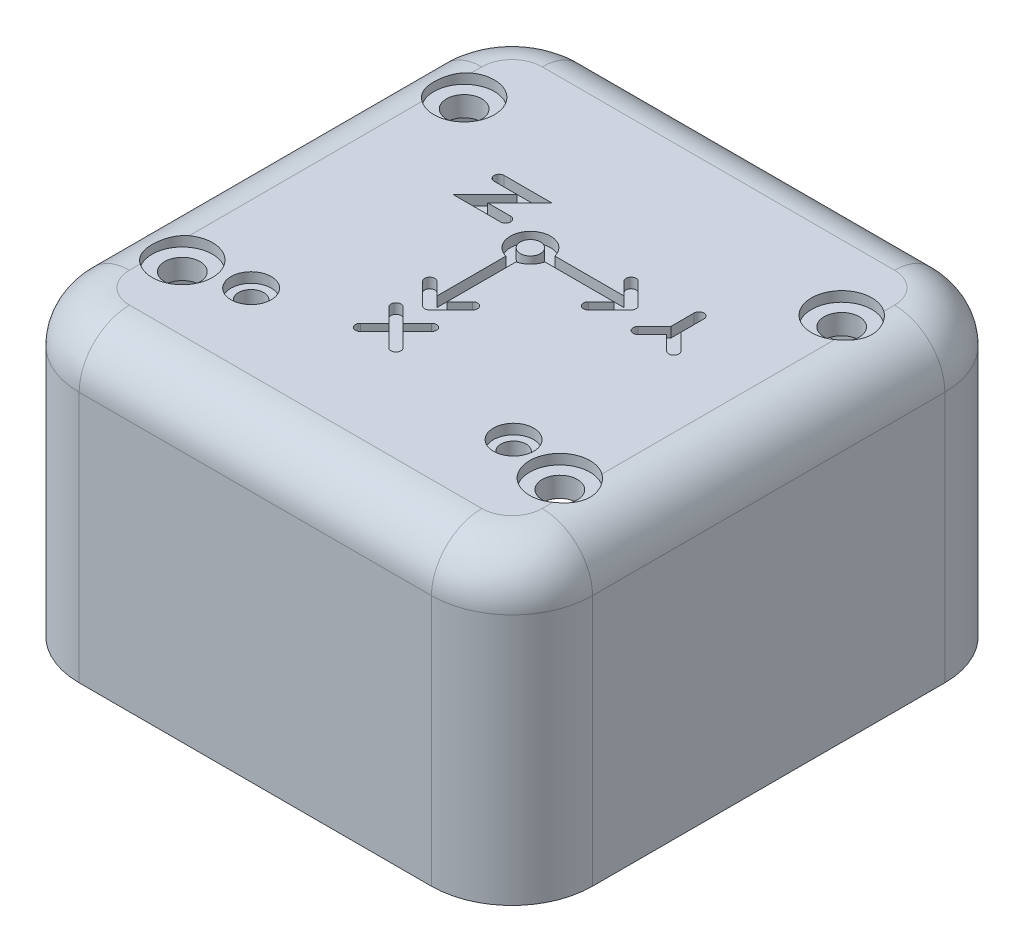
SolidWorks part; units mm, degrees
ref_plane "Front Plane" through (0, 0, 0) normal (0, 0, 1) x (1, 0, 0)
ref_plane "Top Plane" through (0, 0, 0) normal (0, 1, 0) x (1, 0, 0)
ref_plane "Right Plane" through (0, 0, 0) normal (1, 0, 0) x (0, 0, -1)
sketch "Sketch1" plane through (0, 0, 0) normal (0, 1, 0) x (1, 0, 0)
  line L1 (8, 0) -> (43, 0)
  line L2 (0, 8) -> (0, 43)
  line L3 (8, 51) -> (43, 51)
  line L4 (51, 8) -> (51, 43)
  arc A0 (43, 51) -> (51, 43) centre (43, 43) cw
  arc A1 (43, 0) -> (51, 8) centre (43, 8) ccw
  arc A2 (8, 0) -> (0, 8) centre (8, 8) cw
  arc A3 (0, 43) -> (8, 51) centre (8, 43) cw
  point P7 (51, 51)
  point P10 (51, 0)
  point P13 (0, 0)
  point P16 (0, 51)
  dimension "D3" = 8
  dimension "D1" = 51
  dimension "D2" = 51
extrude "Boss-Extrude1" add sketch "Sketch1" along normal blind 30
sketch "Sketch2" plane through (0, 0, 0) normal (0, -1, 0) x (1, 0, 0)
  line L0 (8, 0) -> (43, 0) construction
  line L1 (8, -2) -> (43, -2)
  line L2 (2, -8) -> (2, -43)
  line L3 (8, -49) -> (43, -49)
  line L4 (49, -8) -> (49, -43)
  line L5 (51, -8) -> (51, -43) construction
  line L6 (43, -51) -> (8, -51) construction
  line L7 (0, -43) -> (0, -8) construction
  arc A0 (43, -49) -> (49, -43) centre (43, -43) ccw
  arc A1 (2, -43) -> (8, -49) centre (8, -43) ccw
  arc A2 (43, -2) -> (49, -8) centre (43, -8) cw
  arc A3 (8, -2) -> (2, -8) centre (8, -8) ccw
  dimension "D5" = 6
  dimension "D1" = 2
  dimension "D2" = 2
  dimension "D3" = 2
  dimension "D4" = 2
extrude "Cut-Extrude1" cut sketch "Sketch2" against normal blind 27
sketch "Sketch3" plane through (0, 27, 0) normal (0, -1, 0) x (1, 0, 0)
  line L0 (43, -2) -> (8, -2) construction
  line L1 (9.5, -3.5) -> (41.5, -3.5) construction
  line L2 (3.5, -9.5) -> (3.5, -41.5) construction
  line L3 (9.5, -47.5) -> (41.5, -47.5) construction
  line L4 (47.5, -9.5) -> (47.5, -41.5) construction
  line L5 (2, -8) -> (2, -43) construction
  line L6 (8, -49) -> (43, -49) construction
  line L7 (49, -43) -> (49, -8) construction
  line L8 (25.5, -3.5) -> (25.5, -47.5) construction
  line L21 (3.5, -25.5) -> (47.5, -25.5) construction
  line L23 (9.915, -49) -> (41.085, -49) construction
  line L24 (9.915, -49) -> (9.915, -10) construction
  line L25 (9.915, -10) -> (41.085, -10) construction
  line L26 (41.085, -49) -> (41.085, -10) construction
  arc A0 (41.5, -3.5) -> (47.5, -9.5) centre (41.5, -9.5) cw construction
  arc A1 (41.5, -47.5) -> (47.5, -41.5) centre (41.5, -41.5) ccw construction
  arc A2 (3.5, -41.5) -> (9.5, -47.5) centre (9.5, -41.5) ccw construction
  arc A3 (9.5, -3.5) -> (3.5, -9.5) centre (9.5, -9.5) ccw construction
  circle A4 centre (6.75, -11.5) radius 3.25 construction
  circle A5 centre (6.75, -11.5) radius 1.75
  circle A6 centre (44.25, -11.5) radius 3.25 construction
  circle A7 centre (44.25, -11.5) radius 1.75
  circle A8 centre (44.25, -39.5) radius 3.25 construction
  circle A9 centre (44.25, -39.5) radius 1.75
  circle A10 centre (6.75, -39.5) radius 3.25 construction
  circle A11 centre (6.75, -39.5) radius 1.75
  circle A12 centre (38.655, -12.5) radius 1.25
  circle A13 centre (12.585, -12.5) radius 1.25
  dimension "D5" = 6
  dimension "D6" = 6.5
  dimension "D8" = 3.5
  dimension "D13" = 2.5
  dimension "D16" = 2.5
  dimension "D18" = 26.07
  dimension "D1" = 1.5
  dimension "D2" = 1.5
  dimension "D3" = 1.5
  dimension "D4" = 1.5
  dimension "D7" = 3.25
  dimension "D9" = 8
  dimension "D10" = 31.17
  dimension "D11" = 39
  dimension "D12" = 15.585
  dimension "D14" = 2.43
  dimension "D15" = 2.5
  dimension "D17" = 2.5
extrude "Cut-Extrude2" cut sketch "Sketch3" against normal blind 3
sketch "Sketch4" plane through (0, 30, 0) normal (0, 1, 0) x (1, 0, 0)
  circle A0 centre (44.25, 39.5) radius 3
  circle A1 centre (6.75, 39.5) radius 3
  circle A2 centre (6.75, 11.5) radius 3
  circle A3 centre (12.585, 12.5) radius 2
  circle A4 centre (38.655, 12.5) radius 2
  circle A5 centre (44.25, 11.5) radius 3
  dimension "D1" = 6
  dimension "D2" = 6
  dimension "D3" = 6
  dimension "D4" = 6
  dimension "D5" = 4
  dimension "D6" = 4
extrude "Cut-Extrude3" cut sketch "Sketch4" against normal blind 1
sketch "Sketch5" plane through (0, 0, -49) normal (0, 0, 1) x (1, 0, 0)
  line L0 (8, 15) -> (43, 15) construction
  line L1 (8, 27) -> (8, 0) construction
  line L2 (43, 27) -> (43, 0) construction
  line L3 (8, 27) -> (43, 27) construction
  line L4 (9.915, 15) -> (9.915, 27) construction
  line L5 (17.585, 18) -> (34.085, 18)
  line L6 (16.585, 17) -> (16.585, 15)
  line L7 (17.585, 14) -> (34.085, 14)
  line L8 (35.085, 17) -> (35.085, 15)
  line L9 (41.085, 15) -> (41.085, 27) construction
  line L10 (25.5, 27) -> (25.5, 15) construction
  arc A0 (34.085, 18) -> (35.085, 17) centre (34.085, 17) cw
  arc A1 (34.085, 14) -> (35.085, 15) centre (34.085, 15) ccw
  arc A2 (16.585, 15) -> (17.585, 14) centre (17.585, 15) ccw
  arc A3 (17.585, 18) -> (16.585, 17) centre (17.585, 17) ccw
  point P20 (35.085, 18)
  point P25 (16.585, 14)
  point P28 (16.585, 18)
  dimension "D8" = 1
  dimension "D1" = 12
  dimension "D2" = 4
  dimension "D3" = 1
  dimension "D4" = 18.5
  dimension "D5" = 15.585
  dimension "D6" = 15.585
  dimension "D7" = 6
extrude "Cut-Extrude4" cut sketch "Sketch5" against normal blind 2
fillet "Fillet1" radius 5 8 edges at (48.6569, 30, -2.3431) (25.5, 30, 0) (2.3431, 30, -2.3431) (0, 30, -25.5) (2.3431, 30, -48.6569) (25.5, 30, -51) (48.6569, 30, -48.6569) (51, 30, -25.5)
fillet "Fillet2" radius 1.5 8 edges at (47.2426, 27, -47.2426) (25.5, 27, -49) (3.7574, 27, -47.2426) (2, 27, -25.5) (3.7574, 27, -3.7574) (25.5, 27, -2) (47.2426, 27, -3.7574) (49, 27, -25.5)
sketch "Sketch6" plane through (0, 30, 0) normal (0, 1, 0) x (1, 0, 0)
  line L1 (24.9204, 29.3484) -> (31.7768, 29.3484)
  line L2 (24.9204, 30.3484) -> (31.7768, 30.3484)
  line L3 (23.1569, 17.0253) -> (21.7427, 18.4395)
  line L4 (23.4839, 27.9119) -> (23.4839, 21.0555)
  line L8 (23.3375, 19.4949) -> (25.4588, 21.6162)
  line L9 (22.4839, 21.0555) -> (21.2162, 22.3233)
  line L10 (31.7768, 29.3484) -> (30.509, 28.0807)
  line L11 (33.3375, 30.202) -> (31.2162, 32.3233)
  line L14 (23.4839, 21.0555) -> (24.7517, 22.3233)
  line L15 (22.6304, 19.4949) -> (20.509, 21.6162)
  line L16 (33.3375, 29.4949) -> (31.2162, 27.3736)
  line L17 (31.7768, 30.3484) -> (30.509, 31.6162)
  line L18 (22.4839, 27.9119) -> (22.4839, 21.0555)
  line L24 (25.2782, 14.904) -> (23.864, 16.3182)
  line L25 (21.7427, 14.1969) -> (23.1569, 15.6111)
  line L26 (39.3465, 28.435) -> (37.7252, 30.0564)
  line L27 (36.7252, 30.0564) -> (35.1039, 28.435)
  line L28 (37.7252, 30.0564) -> (37.7252, 32.3493)
  line L29 (19.277, 31.5842) -> (16.9841, 31.5842)
  line L30 (16.9841, 31.5842) -> (20.1661, 34.7662)
  line L31 (20.1661, 34.7662) -> (15.4553, 34.7662)
  line L32 (24.5711, 14.1969) -> (23.1569, 15.6111)
  line L33 (21.0356, 14.904) -> (22.4498, 16.3182)
  line L34 (38.6394, 27.7279) -> (37.2252, 29.1421)
  line L35 (37.2252, 29.1421) -> (35.811, 27.7279)
  line L36 (36.7252, 30.0564) -> (36.7252, 32.3493)
  line L37 (19.277, 30.5842) -> (14.5699, 30.5842)
  line L38 (14.5699, 30.5842) -> (17.7519, 33.7662)
  line L39 (17.7519, 33.7662) -> (15.4553, 33.7662)
  line L41 (23.864, 16.3182) -> (25.2782, 17.7324)
  line L45 (23.1569, 17.0253) -> (24.5711, 18.4395)
  line L47 (22.4498, 16.3182) -> (21.0356, 17.7324)
  arc A1 (23.4839, 27.9119) -> (24.9204, 29.3484) centre (22.9839, 29.8484) ccw
  circle A2 centre (22.9839, 29.8484) radius 1
  arc A3 (33.3375, 30.202) -> (33.3375, 29.4949) centre (32.9839, 29.8484) cw
  arc A4 (22.6304, 19.4949) -> (23.3375, 19.4949) centre (22.9839, 19.8484) ccw
  arc A5 (23.3375, 19.4949) -> (22.6304, 19.4949) centre (22.9839, 19.8484) cw
  arc A6 (25.4588, 21.6162) -> (24.7517, 22.3233) centre (25.1052, 21.9698) ccw
  arc A7 (23.3375, 19.4949) -> (22.6304, 19.4949) centre (22.9839, 19.8484) cw
  arc A8 (21.2162, 22.3233) -> (20.509, 21.6162) centre (20.8626, 21.9698) ccw
  arc A9 (33.3375, 30.202) -> (33.3375, 29.4949) centre (32.9839, 29.8484) cw
  arc A10 (30.509, 28.0807) -> (31.2162, 27.3736) centre (30.8626, 27.7271) ccw
  arc A11 (33.3375, 30.202) -> (33.3375, 29.4949) centre (32.9839, 29.8484) cw
  arc A12 (31.2162, 32.3233) -> (30.509, 31.6162) centre (30.8626, 31.9698) ccw
  arc A13 (25.2782, 14.904) -> (24.5711, 14.1969) centre (24.9247, 14.5504) cw
  arc A14 (24.9204, 30.3484) -> (22.4839, 27.9119) centre (22.9839, 29.8484) ccw
  arc A15 (21.7427, 18.4395) -> (21.0356, 17.7324) centre (21.3891, 18.086) ccw
  arc A16 (21.7427, 14.1969) -> (21.0356, 14.904) centre (21.3891, 14.5504) cw
  arc A17 (25.2782, 17.7324) -> (24.5711, 18.4395) centre (24.9247, 18.086) ccw
  arc A18 (39.3465, 28.435) -> (38.6394, 27.7279) centre (38.993, 28.0815) cw
  arc A21 (35.1039, 28.435) -> (35.811, 27.7279) centre (35.4574, 28.0815) ccw
  arc A23 (37.7252, 32.3493) -> (36.7252, 32.3493) centre (37.2252, 32.3493) ccw
  arc A24 (19.277, 31.5842) -> (19.277, 30.5842) centre (19.277, 31.0842) cw
  arc A25 (15.4553, 34.7662) -> (15.4553, 33.7662) centre (15.4553, 34.2662) ccw
extrude "Cut-Extrude5" cut sketch "Sketch6" against normal blind 1 contours L2 A14 L18 L9 A8 L15 A4 L8 A6 L14 L4 A1 L1 L10 A10 L16 A3 L11 A12 L17 A2 | L31 A25 L39 L38 L37 A24 L29 L30 | L28 A23 L36 L27 A21 L35 L34 A18 L26 | L41 A17 L45 L3 A15 L47 L33 A16 L25 L32 A13 L24 region at (24.2669, 30, -28.5654) region at (23.1569, 30, -16.3182) region at (37.2252, 30, -29.6457) region at (17.3673, 30, -32.6757)
sketch "Sketch7" plane through (0, 0, -51) normal (0, 0, -1) x (-1, 0, 0)
  line L0 (-16.585, 17) -> (-16.585, 15) construction
  line L1 (-35.085, 23) -> (-16.585, 23)
  line L2 (-40.085, 18) -> (-40.085, 14)
  line L3 (-35.085, 9) -> (-16.585, 9)
  line L4 (-11.585, 18) -> (-11.585, 14)
  line L5 (-35.085, 15) -> (-35.085, 17) construction
  line L6 (-34.085, 18) -> (-17.585, 18) construction
  line L7 (-17.585, 14) -> (-34.085, 14) construction
  arc A0 (-16.585, 23) -> (-11.585, 18) centre (-16.585, 18) cw
  arc A1 (-16.585, 9) -> (-11.585, 14) centre (-16.585, 14) ccw
  arc A2 (-40.085, 14) -> (-35.085, 9) centre (-35.085, 14) ccw
  arc A3 (-35.085, 23) -> (-40.085, 18) centre (-35.085, 18) ccw
  dimension "D5" = 5
  dimension "D1" = 5
  dimension "D2" = 5
  dimension "D3" = 5
  dimension "D4" = 5
extrude "Cut-Extrude6" cut sketch "Sketch7" against normal blind 0.8
